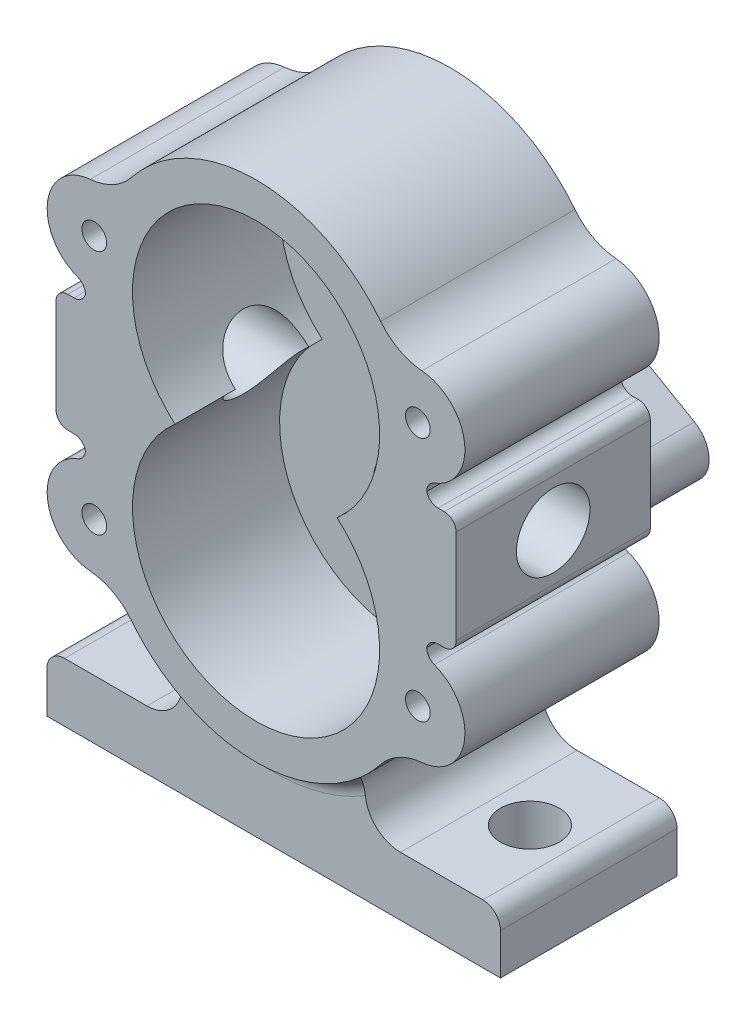
SolidWorks part; units mm, degrees
ref_plane "Front Plane" through (0, 0, 0) normal (0, 0, 1) x (1, 0, 0)
ref_plane "Top Plane" through (0, 0, 0) normal (0, 1, 0) x (1, 0, 0)
ref_plane "Right Plane" through (0, 0, 0) normal (1, 0, 0) x (0, 0, -1)
sketch "Sketch1" plane through (0, 0, 0) normal (0, 0, 1) x (1, 0, 0)
  line L1 (-29, 18.5544) -> (-29, 41.5356)
  line L2 (29, 18.5544) -> (29, 41.5356)
  line L3 (43.6078, 30.045) -> (21.8522, 30.045) construction
  line L4 (-29, 30.045) -> (-64.7654, 30.045) construction
  line L5 (0, -12.8131) -> (0, -74.4568) construction
  arc A0 (21.1874, 62.6391) -> (-21.1874, 62.6391) centre (0, 45.9031) ccw
  arc A1 (-28.1821, 58.874) -> (-30.3, 43.4091) centre (-27.5, 50.9031) ccw
  arc A2 (28.1821, 58.874) -> (30.3, 43.4091) centre (27.5, 50.9031) cw
  arc A3 (28.1821, 1.216) -> (30.3, 16.6809) centre (27.5, 9.1869) ccw
  arc A5 (-28.1821, 1.216) -> (-30.3, 16.6809) centre (-27.5, 9.1869) cw
  arc A6 (21.1874, -2.549) -> (-21.1874, -2.549) centre (0, 14.1869) cw
  arc A7 (29, 41.5356) -> (30.3, 43.4091) centre (31, 41.5356) cw
  arc A8 (30.3, 16.6809) -> (29, 18.5544) centre (31, 18.5544) cw
  arc A9 (-30.3, 16.6809) -> (-29, 18.5544) centre (-31, 18.5544) ccw
  arc A10 (-29, 41.5356) -> (-30.3, 43.4091) centre (-31, 41.5356) ccw
  arc A11 (-28.1821, 1.216) -> (-21.1874, -2.549) centre (-29.0346, -8.7476) cw
  arc A12 (28.1821, 1.216) -> (21.1874, -2.549) centre (29.0346, -8.7476) ccw
  arc A13 (28.1821, 58.874) -> (21.1874, 62.6391) centre (29.0346, 68.8376) cw
  arc A14 (-21.1874, 62.6391) -> (-28.1821, 58.874) centre (-29.0346, 68.8376) cw
  point P5 (-27.5, 50.9031)
  point P8 (-29, 30.045)
  point P18 (29, 30.045)
  point P25 (-29, 30.045)
  point P26 (29, 43.045)
  point P29 (29, 17.045)
  point P33 (-29, 17.045)
  point P36 (-29, 43.045)
  dimension "D1" = 54
  dimension "D4" = 16
  dimension "D2" = 2
  dimension "D5" = 10
  dimension "D3" = 5
  dimension "D6" = 13
extrude "Boss-Extrude1" add sketch "Sketch1" along normal blind 8
sketch "Sketch2" plane through (0, 0, 0) normal (0, 0, -1) x (-1, 0, 0)
  line L0 (-6.5, 25.4452) -> (-18.5, 18.517)
  line L1 (-6.5, 2.9286) -> (-18.5, 9.8568)
  line L2 (6.5, 25.4452) -> (18.5, 18.517)
  line L3 (6.5, 2.9286) -> (18.5, 9.8568)
  circle A0 centre (0, 45.9031) radius 10
  arc A1 (-6.5, 2.9286) -> (6.5, 2.9286) centre (0, 14.1869) ccw
  arc A2 (18.5, 9.8568) -> (18.5, 18.517) centre (16, 14.1869) ccw
  arc A3 (-18.5, 18.517) -> (-18.5, 9.8568) centre (-16, 14.1869) ccw
  arc A4 (6.5, 25.4452) -> (-6.5, 25.4452) centre (0, 14.1869) ccw
  dimension "D1" = 20
  dimension "D2" = 26
  dimension "D3" = 10
  dimension "D4" = 10
  dimension "D5" = 16
  dimension "D6" = 16
extrude "Boss-Extrude2" add sketch "Sketch2" along normal blind 8 contours A0 region at (0, 45.9031, 0)
sketch "Sketch3" plane through (0, 0, 8) normal (0, 0, 1) x (1, 0, 0)
  line L4 (6.5, 2.9286) -> (18.5, 9.8568)
  line L5 (6.5, 2.9286) -> (18.5, 9.8568)
  line L6 (18.5, 18.517) -> (6.5, 25.4452)
  line L7 (18.5, 18.517) -> (6.5, 25.4452)
  line L8 (-6.5, 25.4452) -> (-18.5, 18.517)
  line L9 (-6.5, 25.4452) -> (-18.5, 18.517)
  line L10 (-18.5, 9.8568) -> (-6.5, 2.9286)
  line L11 (-18.5, 9.8568) -> (-6.5, 2.9286)
  arc A1 (-6.5, 2.9286) -> (6.5, 2.9286) centre (0, 14.1869) ccw
  arc A2 (-6.5, 2.9286) -> (6.5, 2.9286) centre (0, 14.1869) ccw
  circle A3 centre (0, 45.9031) radius 10
  circle A4 centre (0, 45.9031) radius 10
  arc A8 (18.5, 9.8568) -> (18.5, 18.517) centre (16, 14.1869) ccw
  arc A9 (18.5, 9.8568) -> (18.5, 18.517) centre (16, 14.1869) ccw
  arc A10 (6.5, 25.4452) -> (-6.5, 25.4452) centre (0, 14.1869) ccw
  arc A11 (6.5, 25.4452) -> (-6.5, 25.4452) centre (0, 14.1869) ccw
  arc A12 (-18.5, 18.517) -> (-18.5, 9.8568) centre (-16, 14.1869) ccw
  arc A13 (-18.5, 18.517) -> (-18.5, 9.8568) centre (-16, 14.1869) ccw
  dimension "D1" = 0
  dimension "D2" = 0
hole_wizard "Ø10.0mm Dowel Hole1" positions "3DSketch1" profile "Sketch4" hole size "Ø10.0" standard "ANSI Metric"
sketch3d "3DSketch1"
  point P0 (0, 45.9031, 8)
  point P3 (0, 14.1869, 8)
sketch "Sketch4" plane through (0, 45.9031, 8) normal (1, 0, 0) x (0, -1, 0)
  line L0 (0, 0) -> (0, 13.1043)
  line L1 (0, 13.1043) -> (5, 10.1)
  line L2 (5, 10.1) -> (5, 0)
  line L5 (5, 0) -> (0, 0)
  line L10 (0, 13.1043) -> (-5, 10.1) construction
  line L11 (0, -6.35) -> (0, 107.95) construction
  dimension "Hole Dia." = 10
  dimension "Hole Depth" = 10.1
  dimension "Drill Angle" = 118
sketch "Sketch5" plane through (0, 0, 8) normal (0, 0, 1) x (1, 0, 0)
  line L2 (-29, 41.5356) -> (-29, 18.5544)
  line L3 (29, 18.5544) -> (29, 41.5356)
  line L4 (-29, 41.5356) -> (-29, 18.5544)
  line L5 (29, 18.5544) -> (29, 41.5356)
  arc A0 (13.7666, 30.045) -> (-13.7666, 30.045) centre (0, 45.9031) ccw
  arc A1 (-13.7666, 30.045) -> (13.7666, 30.045) centre (0, 14.1869) ccw
  arc A16 (-29, 41.5356) -> (-30.3, 43.4091) centre (-31, 41.5356) ccw
  arc A17 (-28.1821, 58.874) -> (-30.3, 43.4091) centre (-27.5, 50.9031) ccw
  arc A18 (-28.1821, 58.874) -> (-21.1874, 62.6391) centre (-29.0346, 68.8376) ccw
  arc A19 (21.1874, 62.6391) -> (-21.1874, 62.6391) centre (0, 45.9031) ccw
  arc A20 (21.1874, 62.6391) -> (28.1821, 58.874) centre (29.0346, 68.8376) ccw
  arc A21 (30.3, 43.4091) -> (28.1821, 58.874) centre (27.5, 50.9031) ccw
  arc A22 (30.3, 43.4091) -> (29, 41.5356) centre (31, 41.5356) ccw
  arc A23 (29, 18.5544) -> (30.3, 16.6809) centre (31, 18.5544) ccw
  arc A24 (28.1821, 1.216) -> (30.3, 16.6809) centre (27.5, 9.1869) ccw
  arc A25 (28.1821, 1.216) -> (21.1874, -2.549) centre (29.0346, -8.7476) ccw
  arc A26 (-21.1874, -2.549) -> (21.1874, -2.549) centre (0, 14.1869) ccw
  arc A27 (-21.1874, -2.549) -> (-28.1821, 1.216) centre (-29.0346, -8.7476) ccw
  arc A28 (-30.3, 16.6809) -> (-28.1821, 1.216) centre (-27.5, 9.1869) ccw
  arc A29 (-30.3, 16.6809) -> (-29, 18.5544) centre (-31, 18.5544) ccw
  arc A30 (-29, 41.5356) -> (-30.3, 43.4091) centre (-31, 41.5356) ccw
  arc A31 (-28.1821, 58.874) -> (-30.3, 43.4091) centre (-27.5, 50.9031) ccw
  arc A32 (-28.1821, 58.874) -> (-21.1874, 62.6391) centre (-29.0346, 68.8376) ccw
  arc A33 (21.1874, 62.6391) -> (-21.1874, 62.6391) centre (0, 45.9031) ccw
  arc A34 (21.1874, 62.6391) -> (28.1821, 58.874) centre (29.0346, 68.8376) ccw
  arc A35 (30.3, 43.4091) -> (28.1821, 58.874) centre (27.5, 50.9031) ccw
  arc A36 (30.3, 43.4091) -> (29, 41.5356) centre (31, 41.5356) ccw
  arc A37 (29, 18.5544) -> (30.3, 16.6809) centre (31, 18.5544) ccw
  arc A38 (28.1821, 1.216) -> (30.3, 16.6809) centre (27.5, 9.1869) ccw
  arc A39 (28.1821, 1.216) -> (21.1874, -2.549) centre (29.0346, -8.7476) ccw
  arc A40 (-21.1874, -2.549) -> (21.1874, -2.549) centre (0, 14.1869) ccw
  arc A41 (-21.1874, -2.549) -> (-28.1821, 1.216) centre (-29.0346, -8.7476) ccw
  arc A42 (-30.3, 16.6809) -> (-28.1821, 1.216) centre (-27.5, 9.1869) ccw
  arc A43 (-30.3, 16.6809) -> (-29, 18.5544) centre (-31, 18.5544) ccw
  dimension "D1" = 42
  dimension "D2" = 42
  dimension "D3" = 0
extrude "Boss-Extrude3" add sketch "Sketch5" along normal blind 25
extrude "Boss-Extrude4" add sketch "Sketch2<3>" along normal blind 23 contours A1 region at (0, 14.1869, 0)
sketch "Sketch2<3>" plane through (0, 0, 0) normal (0, 0, -1) x (-1, 0, 0) same geometry as "Sketch2"
fillet "Fillet2" radius 2 2 edges at (-10, 45.9031, 0) (-10, 45.9031, -8)
sketch "Sketch6" plane through (0, 0, -23) normal (0, 0, -1) x (-1, 0, 0)
  circle A0 centre (0, 14.1869) radius 8
  circle A1 centre (0, 14.1869) radius 13 construction
  dimension "D1" = 16
  dimension "D2" = 5
extrude "Cut-Extrude1" cut sketch "Sketch6" against normal blind 20 contours A0
sketch "Sketch7" plane through (0, 0, 8) normal (0, 0, 1) x (1, 0, 0)
  circle A0 centre (0, 14.1869) radius 5 construction
  circle A1 centre (0, 14.1869) radius 5
extrude "Cut-Extrude2" cut sketch "Sketch7" against normal blind 20
chamfer "Chamfer1" distance 3 angle 45 1 edges at (-8, 14.1869, -3)
hole_wizard "M5x0.8 Tapped Hole1" positions "3DSketch2" profile "Sketch8" tap size "M5x0.8" standard "ANSI Metric"
sketch3d "3DSketch2"
  line L0 (16, 14.1869, -23) -> (16, 14.1869, 0) construction
  line L1 (-16, 14.1869, -23) -> (-16, 14.1869, 0) construction
  point P0 (16, 14.1869, -23)
  point P4 (-16, 14.1869, -23)
sketch "Sketch8" plane through (16, 14.1869, -23) normal (1, 0, 0) x (0, 1, 0)
  line L0 (0, 0) -> (0, 17.2618)
  line L1 (0, 17.2618) -> (2.1, 16)
  line L2 (2.1, 16) -> (2.1, 0)
  line L5 (2.1, 0) -> (0, 0)
  line L10 (0, 17.2618) -> (-2.1, 16) construction
  line L11 (0, -6.35) -> (0, 107.95) construction
  dimension "Tap Drill Dia." = 4.2
  dimension "Tap Drill Depth" = 16
  dimension "Drill Angle" = 118
cosmetic thread "Hole Thread1" parameters "D1"=14, "D2"=5
cosmetic thread "Hole Thread2" parameters "D1"=14, "D2"=5
sketch "Sketch9" plane through (0, 0, 0) normal (0, 0, -1) x (-1, 0, 0)
  line L0 (-21.5407, -16.8131) -> (-38.5407, -16.8131)
  line L1 (-38.5407, -16.8131) -> (-38.5407, -26.8131)
  line L2 (-38.5407, -26.8131) -> (38.5407, -26.8131)
  line L3 (0, 18.1788) -> (0, 10.7028) construction
  line L4 (38.5407, -16.8131) -> (38.5407, -26.8131)
  line L5 (21.5407, -16.8131) -> (38.5407, -16.8131)
  arc A0 (-21.5407, -16.8131) -> (-17.6242, -6.2676) centre (-21.5407, -10.8131) ccw
  arc A1 (-21.1874, -2.549) -> (21.1874, -2.549) centre (0, 14.1869) ccw construction
  arc A2 (-17.6242, -6.2676) -> (17.6242, -6.2676) centre (0, 14.1869) ccw
  arc A3 (21.5407, -16.8131) -> (17.6242, -6.2676) centre (21.5407, -10.8131) cw
  point P0 (-21.5407, -10.8131)
  point P1 (-27.5, 9.1869)
  point P23 (0, -26.8131)
  dimension "D3" = 12
  dimension "D4" = 10
  dimension "D1" = 20
  dimension "D2" = 17
extrude "Boss-Extrude5" add sketch "Sketch9" against normal blind 30
fillet "Fillet3" radius 3 2 edges at (-38.5407, -16.8131, 15) (38.5407, -16.8131, 15)
sketch "Sketch10" plane through (0, -16.8131, 0) normal (0, 1, 0) x (1, 0, 0)
  line L0 (38.5407, 0) -> (38.5407, -30) construction
  circle A0 centre (28.5407, -15) radius 5
  circle A1 centre (-28.5407, -15) radius 5
  dimension "D1" = 10
  dimension "D3" = 10
  dimension "D2" = 10
extrude "Cut-Extrude3" cut sketch "Sketch10" against normal blind 30
sketch "Sketch11" plane through (0, 0, 0) normal (0, 0, -1) x (-1, 0, 0)
  line L0 (0, 16.7587) -> (0, -31.8645) construction
  line L1 (18, -26.8131) -> (8.5917, -12.374)
  line L2 (-38.5407, -26.8131) -> (38.5407, -26.8131) construction
  line L3 (6.9161, -11.4658) -> (-6.9161, -11.4658)
  line L4 (-18, -26.8131) -> (-8.5917, -12.374)
  line L5 (18, -26.8131) -> (-18, -26.8131)
  arc A0 (8.5917, -12.374) -> (6.9161, -11.4658) centre (6.9161, -13.4658) ccw
  arc A1 (-8.5917, -12.374) -> (-6.9161, -11.4658) centre (-6.9161, -13.4658) cw
  point P11 (8, -11.4658)
  point P13 (0, -11.4658)
  dimension "D3" = 2
  dimension "D1" = 18
  dimension "D2" = 8
extrude "Cut-Extrude4" cut sketch "Sketch11" against normal blind 20
sketch "Sketch12" plane through (0, 0, 0) normal (0, 0, -1) x (-1, 0, 0)
  line L4 (18, -26.8131) -> (8.5917, -12.374)
  line L5 (6.9161, -11.4658) -> (-6.9161, -11.4658)
  line L6 (-8.5917, -12.374) -> (-18, -26.8131)
  line L7 (-18, -26.8131) -> (18, -26.8131)
  line L8 (18, -26.8131) -> (8.5917, -12.374)
  line L9 (6.9161, -11.4658) -> (-6.9161, -11.4658)
  line L10 (-8.5917, -12.374) -> (-18, -26.8131)
  line L11 (-18, -26.8131) -> (18, -26.8131)
  arc A2 (8.5917, -12.374) -> (6.9161, -11.4658) centre (6.9161, -13.4658) ccw
  arc A3 (-6.9161, -11.4658) -> (-8.5917, -12.374) centre (-6.9161, -13.4658) ccw
  arc A4 (8.5917, -12.374) -> (6.9161, -11.4658) centre (6.9161, -13.4658) ccw
  arc A5 (-6.9161, -11.4658) -> (-8.5917, -12.374) centre (-6.9161, -13.4658) ccw
  dimension "D1" = 0
extrude "Boss-Extrude6" add sketch "Sketch12" against normal blind 10
fillet "Fillet4" radius 3 1 edges at (0, -12.8131, 30)
sketch "Sketch13" plane through (0, 0, 0) normal (0, 0, -1) x (-1, 0, 0)
  line L0 (-29, 18.5544) -> (-29, 41.5356) construction
  line L1 (-34, 40.045) -> (-34, 20.045)
  line L2 (-34, 40.045) -> (-29, 40.045)
  line L3 (-29, 40.045) -> (-29, 20.045)
  line L4 (-29, 20.045) -> (-34, 20.045)
  line L6 (29, 20.045) -> (34, 20.045)
  line L7 (29, 40.045) -> (29, 20.045)
  line L8 (34, 40.045) -> (29, 40.045)
  line L9 (34, 40.045) -> (34, 20.045)
  point P0 (-34, 30.045)
  dimension "D1" = 5
  dimension "D2" = 20
  dimension "D3" = 10
extrude "Boss-Extrude7" add sketch "Sketch13" against normal up to vertex (33 mm away) up to point (29, 18.5544, 33)
fillet "Fillet5" radius 2 8 edges at (-29, 20.045, 16.5) (-34, 20.045, 16.5) (-34, 40.045, 16.5) (-29, 40.045, 16.5) (29, 20.045, 16.5) (29, 40.045, 16.5) (34, 20.045, 16.5) (34, 40.045, 16.5)
sketch "Sketch15" plane through (34, 0, 0) normal (1, 0, 0) x (0, 0, -1)
  point P0 (-16.5, 30.045)
hole_wizard "M14x1.5 Tapped Hole1" positions "3DSketch4" profile "Sketch16" tap size "M14x1.5" standard "ANSI Metric" end condition through all
sketch3d "3DSketch4"
  point P0 (34, 30.045, 16.5)
sketch "Sketch16" plane through (34, 30.045, 16.5) normal (0, 1, 0) x (0, 0, -1)
  line L0 (0, 0) -> (0, 72.5407)
  line L1 (0, 72.5407) -> (6.25, 72.5407)
  line L2 (6.25, 72.5407) -> (6.25, 0)
  line L5 (6.25, 0) -> (0, 0)
  line L11 (0, -6.35) -> (0, 107.95) construction
  dimension "Thru Tap Drill Dia." = 12.5
  dimension "Thru Tap Drill Depth" = 72.5407
cosmetic thread "Hole Thread3" parameters "D2"=14
sketch "Sketch17" plane through (0, 0, 33) normal (0, 0, 1) x (1, 0, 0)
  point P0 (27.5, 50.9031)
  point P1 (-27.5, 50.9031)
  point P3 (-27.5, 9.1869)
  point P5 (27.5, 9.1869)
hole_wizard "M5x0.8 Tapped Hole2" positions "3DSketch5" profile "Sketch18" tap size "M5x0.8" standard "ANSI Metric"
sketch3d "3DSketch5"
  point P0 (-27.5, 50.9031, 33)
  point P3 (27.5, 50.9031, 33)
  point P6 (27.5, 9.1869, 33)
  point P9 (-27.5, 9.1869, 33)
sketch "Sketch18" plane through (-27.5, 50.9031, 33) normal (1, 0, 0) x (0, -1, 0)
  line L0 (0, 0) -> (0, 21.2618)
  line L1 (0, 21.2618) -> (2.1, 20)
  line L2 (2.1, 20) -> (2.1, 0)
  line L5 (2.1, 0) -> (0, 0)
  line L10 (0, 21.2618) -> (-2.1, 20) construction
  line L11 (0, -6.35) -> (0, 107.95) construction
  dimension "Tap Drill Dia." = 4.2
  dimension "Tap Drill Depth" = 20
  dimension "Drill Angle" = 118
cosmetic thread "Hole Thread4" parameters "D1"=16, "D2"=5
cosmetic thread "Hole Thread5" parameters "D1"=16, "D2"=5
cosmetic thread "Hole Thread6" parameters "D1"=16, "D2"=5
cosmetic thread "Hole Thread7" parameters "D1"=16, "D2"=5
sketch "Sketch19" plane through (0, 0, 33) normal (0, 0, 1) x (1, 0, 0)
  circle A0 centre (0, 45.9031) radius 15.86
  circle A1 centre (0, 14.1869) radius 15.8562
  point P6 (0, 0)
  dimension "D1" = 31.7162
  dimension "D2" = 31.72
